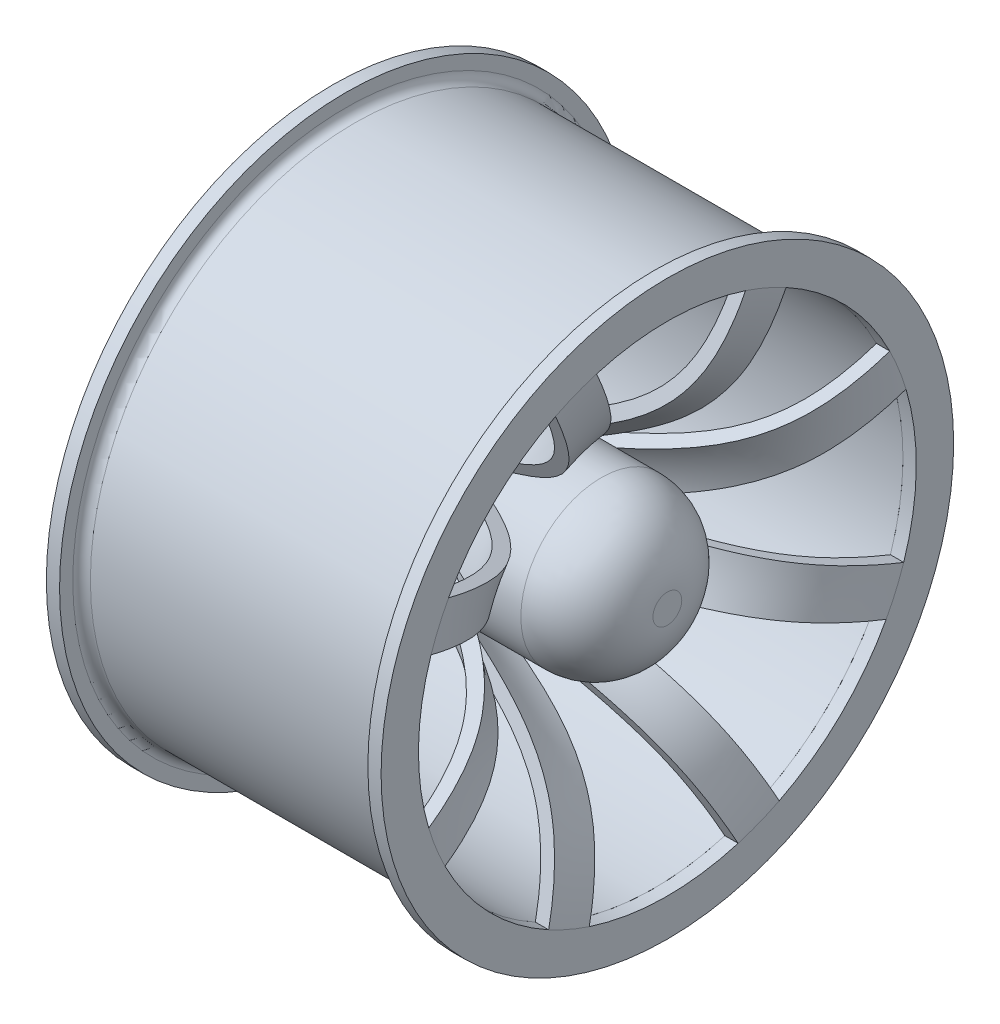
SolidWorks part; units mm, degrees
ref_plane "Front Plane" through (0, 0, 0) normal (0, 0, 1) x (1, 0, 0)
ref_plane "Top Plane" through (0, 0, 0) normal (0, 1, 0) x (1, 0, 0)
ref_plane "Right Plane" through (0, 0, 0) normal (1, 0, 0) x (0, 0, -1)
sketch "Sketch2" plane through (0, 0, 0) normal (0, 0, 1) x (1, 0, 0)
  line L0 (0, 102.4158) -> (0, 0) construction
  line L1 (-38, 65) -> (-35, 65)
  line L2 (-35, 65) -> (-35, 62)
  line L3 (-33, 60) -> (33, 60)
  line L4 (-38, 65) -> (-38, 56.5133)
  line L5 (-38, 56.5133) -> (34.9836, 56.5133)
  line L6 (35, 65) -> (35, 62)
  line L7 (38, 65) -> (35, 65)
  line L8 (38, 65) -> (38, 56.5133)
  line L9 (0, 0) -> (104.8161, 0) construction
  line L10 (-0.0126, 18.267) -> (0, 15)
  line L11 (35.0155, 56.8183) -> (34.9836, 56.5133)
  arc A0 (35, 62) -> (33, 60) centre (33, 62) cw
  arc A1 (-35, 62) -> (-33, 60) centre (-33, 62) ccw
  spline S0 degree 3 poles (38, 56.5133) (37.5141, 51.7597) (33.0497, 30.8782) (17.6686, 22.6711) (0, 15) knots 0 0 0 0 0.221557 1 1 1 1
  spline S1 degree 1 poles (35.0155, 56.8183) (-1.1948, 17.7518) knots 0 0 1 1 construction
  spline S2 degree 3 poles (35.0155, 56.8183) (34.8858, 55.549) (34.5463, 52.9959) (33.5656, 48.1164) (31.7781, 42.6007) (28.7576, 37.2184) (24.8244, 32.6264) (19.9002, 28.5825) (14.9326, 25.4991) (10.4437, 23.1154) (6.8253, 21.346) (3.5987, 19.8644) (1.3791, 18.878) (0.2901, 18.3994) (-0.4026, 18.0963) (-0.9007, 17.8795) (-1.1948, 17.7518) knots 0 0 0 0 0.0625 0.125 0.25 0.375 0.5 0.625 0.75 0.8125 0.875 0.9375 0.96875 0.977996 0.986797 1 1 1 1 only from (35.0155, 56.8183) to (-0.0126, 18.267)
  point P9 (0, 60)
  point P13 (0, 56.5133)
  point P15 (35, 60)
  point P18 (-35, 60)
  dimension "D4" = 2
  dimension "D1" = 3
  dimension "D2" = 70
  dimension "D3" = 5
  dimension "D5" = 60
  dimension "D7" = 15
  dimension "D6" = 3
revolve "Revolve1" add sketch "Sketch2" angle 360 about L9
sketch "Sketch3" plane through (-38, 0, 0) normal (-1, 0, 0) x (0, 0, 1)
  circle A0 centre (0, 0) radius 18.267 construction
  circle A1 centre (0, 0) radius 18.267
  circle A2 centre (0, 0) radius 15 construction
  circle A3 centre (0, 0) radius 15
extrude "Boss-Extrude1" add sketch "Sketch3" against normal blind 60
sketch "Sketch5" plane through (38, 0, 0) normal (1, 0, 0) x (0, 0, -1)
  circle A0 centre (0, 0) radius 18.267 construction
  circle A1 centre (0, 0) radius 18.267
extrude "Boss-Extrude2" add sketch "Sketch5" against normal blind 20
sketch "Sketch6" plane through (38, 0, 0) normal (1, 0, 0) x (0, 0, -1)
  line L0 (-8.2104, 16.3179) -> (-25.4007, 50.4832)
  line L1 (-16.0669, 54.1812) -> (2.0622, 18.1502)
  line L2 (26.9509, 49.6729) -> (14.2923, 11.376)
  line L3 (5.7329, 17.3441) -> (17.736, 53.658)
  line L4 (54.1812, 16.0669) -> (18.1502, -2.0622)
  line L5 (16.3179, 8.2104) -> (50.4832, 25.4007)
  line L6 (49.6729, -26.9509) -> (11.376, -14.2923)
  line L7 (17.3441, -5.7329) -> (53.658, -17.736)
  line L8 (16.0669, -54.1812) -> (-2.0622, -18.1502)
  line L9 (8.2104, -16.3179) -> (25.4007, -50.4832)
  line L10 (-26.9509, -49.6729) -> (-14.2923, -11.376)
  line L11 (-5.7329, -17.3441) -> (-17.736, -53.658)
  line L12 (-54.1812, -16.0669) -> (-18.1502, 2.0622)
  line L13 (-16.3179, -8.2104) -> (-50.4832, -25.4007)
  line L14 (-49.6729, 26.9509) -> (-11.376, 14.2923)
  line L15 (-17.3441, 5.7329) -> (-53.658, 17.736)
  circle A0 centre (0, 0) radius 18.267 construction
  circle A1 centre (0, 0) radius 18.267
  circle A2 centre (0, 0) radius 56.5133 construction
  circle A3 centre (0, 0) radius 56.5133
  circle M18 centre (0, 0) radius 56.5133
  dimension "D1" = 10
  dimension "D2" = 8
extrude "Cut-Extrude1" cut sketch "Sketch6" against normal through all contours A1 L0 L10 M18 | A1 L3 L1 M18 | A1 L5 L2 M18 | A1 L7 L4 M18 | A1 L9 L6 M18 | A1 L11 L8 M18 | A1 L15 L12 M18 | A1 L13 L10 M18 region at (38, 30.9445, 28.2304) region at (38, 41.843, -1.9192) region at (38, 1.9192, 41.843) region at (38, 28.2304, -30.9445) region at (38, -28.2304, 30.9445) region at (38, -1.9192, -41.843) region at (38, -41.843, 1.9192) region at (38, -30.9445, -28.2304)
fillet "Fillet1" radius 15 2 edges at (38, 0, -18.267) (18, 0, -15)
